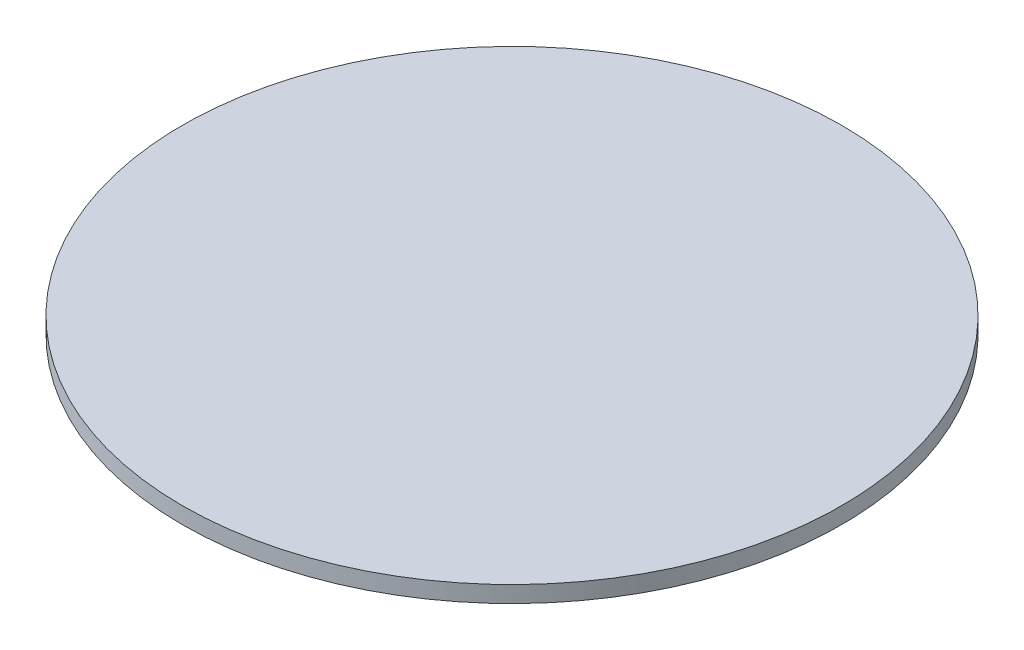
SolidWorks part; units mm, degrees
ref_plane "Front Plane" through (0, 0, 0) normal (0, 0, 1) x (1, 0, 0)
ref_plane "Top Plane" through (0, 0, 0) normal (0, 1, 0) x (1, 0, 0)
ref_plane "Right Plane" through (0, 0, 0) normal (1, 0, 0) x (0, 0, -1)
sketch "Sketch1" plane through (0, 0, 0) normal (0, 1, 0) x (1, 0, 0)
  circle A0 centre (0, 0) radius 300
  dimension "D1" = 600
extrude "Boss-Extrude1" add sketch "Sketch1" along normal blind 15
